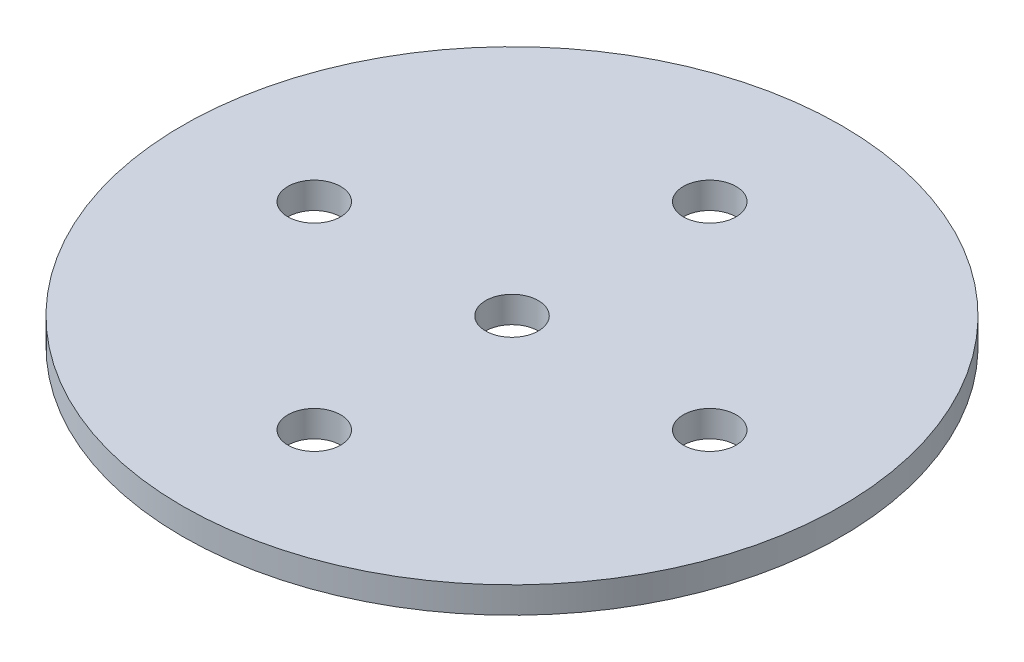
SolidWorks part; units mm, degrees
ref_plane "Front Plane" through (0, 0, 0) normal (0, 0, 1) x (1, 0, 0)
ref_plane "Top Plane" through (0, 0, 0) normal (0, 1, 0) x (1, 0, 0)
ref_plane "Right Plane" through (0, 0, 0) normal (1, 0, 0) x (0, 0, -1)
sketch "Sketch1" plane through (0, 0, 0) normal (0, 1, 0) x (1, 0, 0)
  line L0 (120, 0) -> (-120, 0) construction
  line L1 (0, 120) -> (0, -120) construction
  circle A0 centre (0, 0) radius 10
  circle A1 centre (75, 0) radius 10
  circle A2 centre (0, -75) radius 10
  circle A3 centre (-75, 0) radius 10
  circle A4 centre (0, 75) radius 10
  circle A5 centre (0, 0) radius 125
  dimension "D1" = 20
  dimension "D6" = 250
  dimension "D2" = 75
  dimension "D3" = 75
  dimension "D4" = 75
  dimension "D5" = 75
extrude "Boss-Extrude1" add sketch "Sketch1" along normal blind 10
